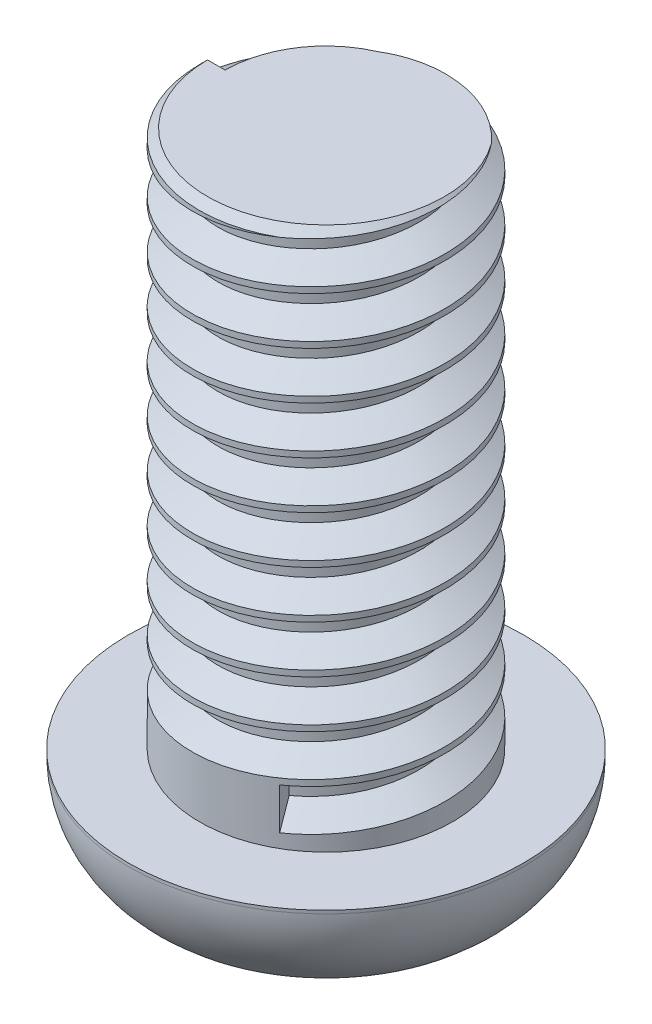
SolidWorks part; units mm, degrees
ref_plane "Front" through (0, 0, 0) normal (0, 0, 1) x (1, 0, 0)
ref_plane "Top" through (0, 0, 0) normal (0, 1, 0) x (1, 0, 0)
ref_plane "Right" through (0, 0, 0) normal (1, 0, 0) x (0, 0, -1)
sketch "Sketch1" plane through (0, 0, 0) normal (0, 0, 1) x (1, 0, 0)
  line L0 (0, 0) -> (11.8997, 0) construction
  line L1 (0, 0) -> (0, 11.9896) construction
  line L2 (6.25, 3.3) -> (6.25, 3.2)
  line L3 (4, 0) -> (1.5526, 0) construction
  line L4 (6.25, 3.3) -> (4, 3.3)
  line L5 (4, 3.3) -> (4, 20.3)
  line L6 (4, 20.3) -> (0, 20.3)
  line L7 (0, 20.3) -> (0, 0)
  line L9 (0, 0) -> (4, 0)
  line L10 (6.25, 3.2) -> (6.25, 2.7422) construction
  arc A0 (6.25, 3.2) -> (4, 0) centre (2.8494, 3.2) cw
  point P12 (0, 0)
  dimension "D5" = 3.3
  dimension "D2" = 4
  dimension "D3" = 17
  dimension "D4" = 2.25
  dimension "D1" = 0.1
revolve "Revolve1" add sketch "Sketch1" angle 360 about L1
sketch "Sketch3" plane through (0, 0, 0) normal (0, -1, 0) x (1, 0, 0)
  line L0 (0, 0) -> (0, 2.3094) construction
  line L1 (0, 2.3094) -> (-2, 1.1547)
  line L2 (-2, 1.1547) -> (-2, -1.1547)
  line L3 (-2, -1.1547) -> (0, -2.3094)
  line L4 (0, -2.3094) -> (2, -1.1547)
  line L5 (2, -1.1547) -> (2, 1.1547)
  line L6 (2, 1.1547) -> (0, 2.3094)
  circle A0 centre (0, 0) radius 2 construction
  circle A1 centre (0, 0) radius 4 construction
  dimension "D1" = 4
extrude "Cut-Extrude2" cut sketch "Sketch3" against normal offset from surface (2.792 mm away) 0.508 up to face at (0, 3.3, -4)
chamfer "Chamfer1" distance 0.254 angle 45 1 edges at (0, 20.3, -4)
sketch "Sketch4" plane through (0, 0, 0) normal (0, -1, 0) x (1, 0, 0)
  circle A0 centre (0, 0) radius 2.3094
extrude "Cut-Extrude3" cut sketch "Sketch4" against normal up to next (2.792 mm away) draft 65
sketch "Sketch7" plane through (0, 2.792, 0) normal (0, -1, 0) x (1, 0, 0)
  line L0 (-2, -1.1547) -> (-2, 1.1547) construction
  circle A0 centre (0, 0) radius 2
extrude "Cut-Extrude5" cut sketch "Sketch7" against normal blind 0.25 draft 75
thread "Thread1" pitch 1.5 method cut profile "Thread Profile1" start angle 0, offset 1, length 16, pitch 1.5, diameter 8
ref_plane "Plane1" through (-4, 21.046, 0) normal (0, 0, 1) x (-1, 0, 0)
sketch "Thread Profile1" plane through (-4, 21.046, 0) normal (0, 0, 1) x (-1, 0, 0)
  line L0 (0, 0) -> (0, 1.5) construction
  line L11 (0, 0) -> (0, 1.3125)
  line L12 (0, 1.3125) -> (-0.8119, 0.8437)
  line L13 (-0.8119, 0.8437) -> (-0.8119, 0.4687)
  line L15 (-0.8119, 0.4687) -> (0, 0)
  line L17 (-0.8119, 0.6562) -> (0, 0.6562) construction
  point P2 (0, 0)
  dimension "Pitch" = 1.5
  dimension "Profile_Angle" = 60
  dimension "Profile_Land" = 0.375
  dimension "Profile_Height" = 0.8119
